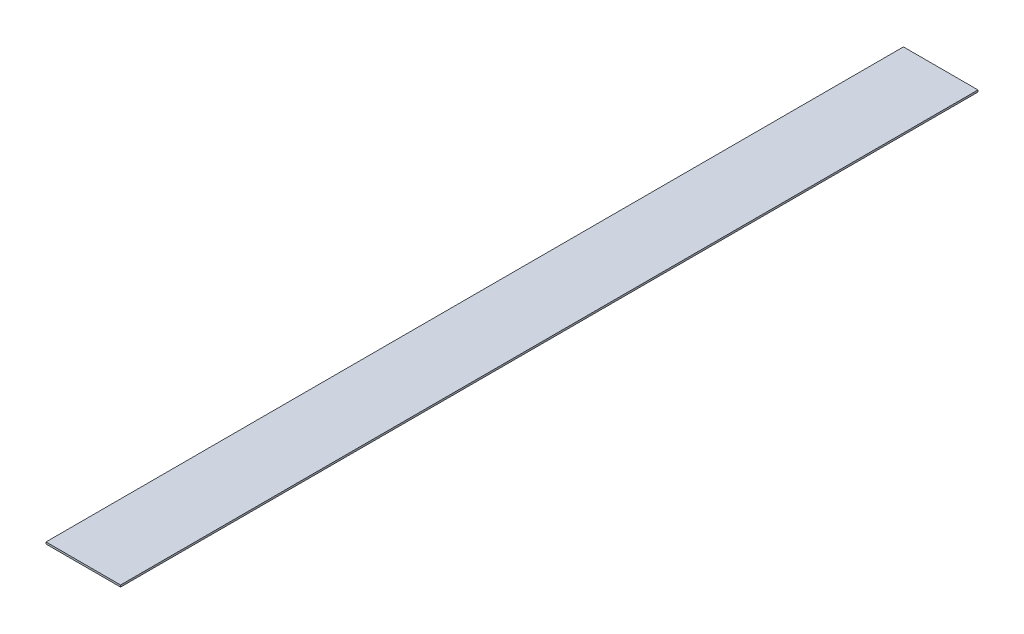
SolidWorks part; units mm, degrees
material "Ст 3 ГОСТ 380-88"
ref_plane "Спереди" through (0, 0, 0) normal (0, 0, 1) x (1, 0, 0)
ref_plane "Сверху" through (0, 0, 0) normal (0, 1, 0) x (1, 0, 0)
ref_plane "Справа" through (0, 0, 0) normal (1, 0, 0) x (0, 0, -1)
sketch "Эскиз1" plane through (0, 0, 0) normal (0, 0, 1) x (1, 0, 0)
  line L1 (-100, 2.5) -> (100, 2.5)
  line L2 (-100, 2.5) -> (-100, -2.5)
  line L3 (-100, -2.5) -> (100, -2.5)
  line L4 (100, 2.5) -> (100, -2.5)
  line L5 (-100, 2.5) -> (100, -2.5) construction
  line L6 (-100, -2.5) -> (100, 2.5) construction
  point P0 (0, 0)
  dimension "Толщина" = 5
  dimension "Ширина" = 200
extrude "Бобышка-Вытянуть1" add sketch "Эскиз1" along normal mid plane 2300
sketch "Эскиз2" plane through (0, -2.5, 0) normal (0, -1, 0) x (1, 0, 0)
  line L0 (0, 1150) -> (0, -1150) construction
  line L1 (-100, 1150) -> (100, 1150) construction
  line L2 (-100, -1150) -> (100, -1150) construction
  line L3 (-100, 0) -> (98.6926, 0) construction
  line L4 (-100, 1150) -> (-100, -1150) construction
ref_axis "Ось1" through (0, -50, 0) along (0, 1, 0)
